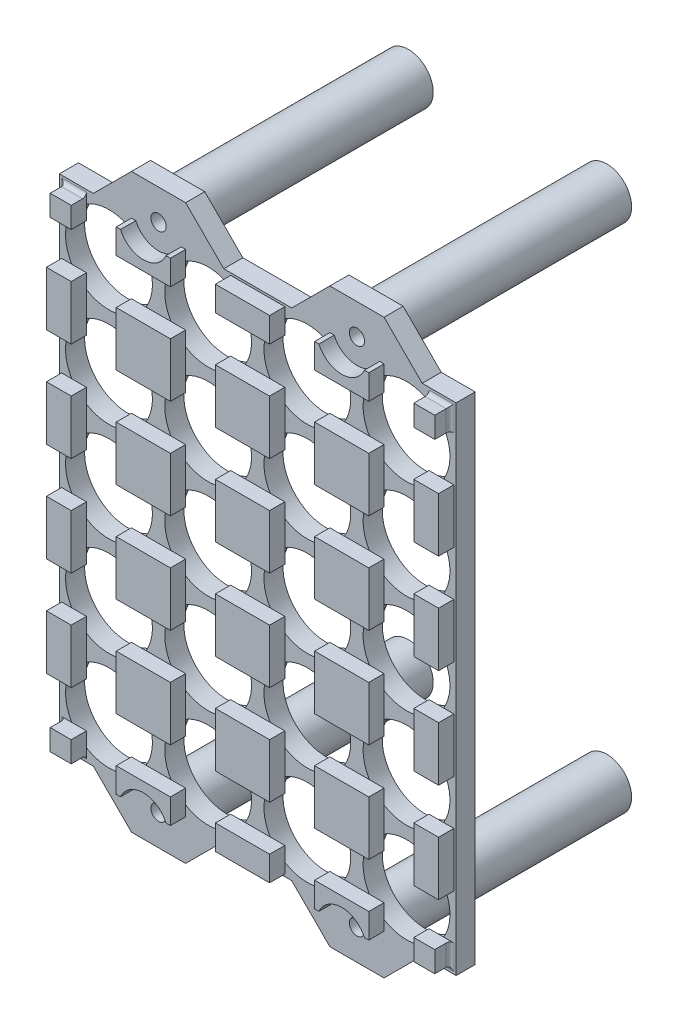
SolidWorks part; units mm, degrees
ref_plane "Front Plane" through (0, 0, 0) normal (0, 0, 1) x (1, 0, 0)
ref_plane "Top Plane" through (0, 0, 0) normal (0, 1, 0) x (1, 0, 0)
ref_plane "Right Plane" through (0, 0, 0) normal (1, 0, 0) x (0, 0, -1)
sketch "Szkic1" plane through (0, 0, 0) normal (0, 0, 1) x (1, 0, 0)
  line L1 (-20.2054, 8.0552) -> (83.7946, 8.0552)
  line L2 (-20.2054, 8.0552) -> (-20.2054, -17.9448)
  line L3 (-20.2054, -17.9448) -> (83.7946, -17.9448)
  line L4 (83.7946, 8.0552) -> (83.7946, -17.9448)
  circle A0 centre (-7.2054, -4.9448) radius 8.854
  circle A1 centre (-7.2054, -4.9448) radius 11.3761
  circle A2 centre (18.7946, -4.9448) radius 8.854
  circle A3 centre (18.7946, -4.9448) radius 11.3761
  circle A4 centre (44.7946, -4.9448) radius 8.854
  circle A5 centre (44.7946, -4.9448) radius 11.3761
  circle A6 centre (70.7946, -4.9448) radius 8.854
  circle A7 centre (70.7946, -4.9448) radius 11.3761
  circle A10 centre (96.7946, -4.9448) radius 8.854 [skipped]
  circle A11 centre (96.7946, -4.9448) radius 11.3761 [skipped]
  dimension "D2" = 13
  dimension "D5" = 13
  dimension "D1" = 5
extrude "Dodanie-wyciągnięcie1" add sketch "Szkic1" along normal blind 5 contours L4 L1 L2 L3 A7 A5 A3 A1 region at (31.7946, -4.9448, 0)
sketch "Szkic15" plane through (0, 0, 0) normal (0, 0, 1) x (1, 0, 0)
  line L6 (-20.2054, -4.9448) -> (-32.3088, -4.9448)
  line L41 (-18.6054, 6.4552) -> (-13.1054, 6.4552)
  line L42 (-18.6054, 6.4552) -> (-18.6054, 0.9552)
  line L43 (-18.6054, 0.9552) -> (-13.1054, 0.9552)
  line L44 (-13.1054, 6.4552) -> (-13.1054, 0.9552)
  line L45 (4.1946, 0.9552) -> (-1.3054, 0.9552)
  line L46 (4.1946, 6.4552) -> (4.1946, 0.9552)
  line L47 (4.1946, 6.4552) -> (-1.3054, 6.4552)
  line L48 (-1.3054, 6.4552) -> (-1.3054, 0.9552)
  line L49 (7.3946, 0.9552) -> (12.8946, 0.9552)
  line L50 (12.8946, 6.4552) -> (12.8946, 0.9552)
  line L51 (7.3946, 6.4552) -> (12.8946, 6.4552)
  line L52 (7.3946, 6.4552) -> (7.3946, 0.9552)
  line L53 (30.1946, 6.4552) -> (24.6946, 6.4552)
  line L54 (24.6946, 6.4552) -> (24.6946, 0.9552)
  line L55 (30.1946, 6.4552) -> (30.1946, 0.9552)
  line L56 (30.1946, 0.9552) -> (24.6946, 0.9552)
  line L57 (33.3946, 0.9552) -> (38.8946, 0.9552)
  line L58 (38.8946, 6.4552) -> (38.8946, 0.9552)
  line L59 (33.3946, 6.4552) -> (38.8946, 6.4552)
  line L60 (33.3946, 6.4552) -> (33.3946, 0.9552)
  line L61 (56.1946, 6.4552) -> (50.6946, 6.4552)
  line L62 (50.6946, 6.4552) -> (50.6946, 0.9552)
  line L63 (56.1946, 6.4552) -> (56.1946, 0.9552)
  line L64 (56.1946, 0.9552) -> (50.6946, 0.9552)
  line L65 (59.3946, 0.9552) -> (64.8946, 0.9552)
  line L66 (64.8946, 6.4552) -> (64.8946, 0.9552)
  line L67 (59.3946, 6.4552) -> (64.8946, 6.4552)
  line L68 (59.3946, 6.4552) -> (59.3946, 0.9552)
  line L69 (82.1946, 6.4552) -> (76.6946, 6.4552)
  line L70 (76.6946, 6.4552) -> (76.6946, 0.9552)
  line L71 (82.1946, 6.4552) -> (82.1946, 0.9552)
  line L72 (82.1946, 0.9552) -> (76.6946, 0.9552)
  line L105 (56.1946, -7.5448) -> (50.6946, -7.5448) [skipped]
  line L106 (56.1946, -7.5448) -> (56.1946, -13.0448) [skipped]
  line L107 (56.1946, -13.0448) -> (50.6946, -13.0448) [skipped]
  line L108 (59.3946, -13.0448) -> (64.8946, -13.0448) [skipped]
  line L109 (64.8946, -7.5448) -> (64.8946, -13.0448) [skipped]
  line L110 (59.3946, -7.5448) -> (64.8946, -7.5448) [skipped]
  line L111 (59.3946, -7.5448) -> (59.3946, -13.0448) [skipped]
  line L112 (82.1946, -7.5448) -> (76.6946, -7.5448) [skipped]
  line L113 (76.6946, -7.5448) -> (76.6946, -13.0448) [skipped]
  line L114 (82.1946, -7.5448) -> (82.1946, -13.0448) [skipped]
  line L115 (82.1946, -13.0448) -> (76.6946, -13.0448) [skipped]
  line L116 (7.3946, -13.0448) -> (12.8946, -13.0448) [skipped]
  line L117 (12.8946, -7.5448) -> (12.8946, -13.0448) [skipped]
  line L118 (7.3946, -7.5448) -> (12.8946, -7.5448) [skipped]
  line L119 (7.3946, -7.5448) -> (7.3946, -13.0448) [skipped]
  line L120 (30.1946, -7.5448) -> (24.6946, -7.5448) [skipped]
  line L121 (24.6946, -7.5448) -> (24.6946, -13.0448) [skipped]
  line L122 (30.1946, -7.5448) -> (30.1946, -13.0448) [skipped]
  line L123 (30.1946, -13.0448) -> (24.6946, -13.0448) [skipped]
  line L124 (33.3946, -13.0448) -> (38.8946, -13.0448) [skipped]
  line L125 (38.8946, -7.5448) -> (38.8946, -13.0448) [skipped]
  line L126 (33.3946, -7.5448) -> (38.8946, -7.5448) [skipped]
  line L127 (33.3946, -7.5448) -> (33.3946, -13.0448) [skipped]
  line L128 (50.6946, -7.5448) -> (50.6946, -13.0448) [skipped]
  line L129 (-18.6054, -13.0448) -> (-13.1054, -13.0448) [skipped]
  line L130 (-13.1054, -7.5448) -> (-13.1054, -13.0448) [skipped]
  line L131 (-18.6054, -7.5448) -> (-13.1054, -7.5448) [skipped]
  line L132 (-18.6054, -7.5448) -> (-18.6054, -13.0448) [skipped]
  line L133 (4.1946, -7.5448) -> (-1.3054, -7.5448) [skipped]
  line L134 (-1.3054, -7.5448) -> (-1.3054, -13.0448) [skipped]
  line L135 (4.1946, -7.5448) -> (4.1946, -13.0448) [skipped]
  line L136 (4.1946, -13.0448) -> (-1.3054, -13.0448) [skipped]
  line L138 (82.1946, -10.8448) -> (76.6946, -10.8448)
  line L139 (82.1946, -16.3448) -> (82.1946, -10.8448)
  line L140 (76.6946, -16.3448) -> (76.6946, -10.8448)
  line L141 (82.1946, -16.3448) -> (76.6946, -16.3448)
  line L142 (59.3946, -16.3448) -> (59.3946, -10.8448)
  line L143 (59.3946, -16.3448) -> (64.8946, -16.3448)
  line L144 (64.8946, -16.3448) -> (64.8946, -10.8448)
  line L145 (59.3946, -10.8448) -> (64.8946, -10.8448)
  line L146 (56.1946, -10.8448) -> (50.6946, -10.8448)
  line L147 (56.1946, -16.3448) -> (56.1946, -10.8448)
  line L148 (50.6946, -16.3448) -> (50.6946, -10.8448)
  line L149 (56.1946, -16.3448) -> (50.6946, -16.3448)
  line L150 (33.3946, -16.3448) -> (33.3946, -10.8448)
  line L151 (33.3946, -16.3448) -> (38.8946, -16.3448)
  line L152 (38.8946, -16.3448) -> (38.8946, -10.8448)
  line L153 (33.3946, -10.8448) -> (38.8946, -10.8448)
  line L154 (30.1946, -10.8448) -> (24.6946, -10.8448)
  line L155 (30.1946, -16.3448) -> (30.1946, -10.8448)
  line L156 (24.6946, -16.3448) -> (24.6946, -10.8448)
  line L157 (30.1946, -16.3448) -> (24.6946, -16.3448)
  line L158 (7.3946, -16.3448) -> (7.3946, -10.8448)
  line L159 (7.3946, -16.3448) -> (12.8946, -16.3448)
  line L160 (12.8946, -16.3448) -> (12.8946, -10.8448)
  line L161 (7.3946, -10.8448) -> (12.8946, -10.8448)
  line L162 (-1.3054, -16.3448) -> (-1.3054, -10.8448)
  line L163 (4.1946, -16.3448) -> (-1.3054, -16.3448)
  line L164 (4.1946, -16.3448) -> (4.1946, -10.8448)
  line L165 (4.1946, -10.8448) -> (-1.3054, -10.8448)
  line L166 (-13.1054, -16.3448) -> (-13.1054, -10.8448)
  line L167 (-18.6054, -10.8448) -> (-13.1054, -10.8448)
  line L168 (-18.6054, -16.3448) -> (-18.6054, -10.8448)
  line L169 (-18.6054, -16.3448) -> (-13.1054, -16.3448)
  point P5 (-18.6054, 6.4552)
  point P71 (-18.6054, -16.3448)
  dimension "D1" = 5.5
extrude "Dodanie-wyciągnięcie7" add sketch "Szkic15" along normal blind 4 from surface contours L167 L166 L169 L168 | L41 L44 L43 L42 | L47 L48 L45 L46 | L51 L50 L49 L52 | L165 L162 L163 L164 | L161 L160 L159 L158 | L53 L54 L56 L55 | L59 L58 L57 L60 | L153 L152 L151 L150 | L154 L156 L157 L155 | L61 L62 L64 L63 | L67 L66 L65 L68 | L145 L144 L143 L142 | L146 L148 L149 L147 | L69 L70 L72 L71 | L138 L140 L141 L139 starting at face at (82.1707, -4.9448, 5)
fillet "Zaokrąglenie9" radius 1 32 edges at (82.1946, 3.7052, 5) (79.4446, 6.4552, 5) (82.1946, -13.5948, 5) (79.4446, -16.3448, 5) (59.3946, 3.7052, 5) (62.1446, 6.4552, 5) (59.3946, -13.5948, 5) (62.1446, -16.3448, 5) (53.4446, -16.3448, 5) (56.1946, -13.5948, 5) (56.1946, 3.7052, 5) (53.4446, 6.4552, 5) (36.1446, 6.4552, 5) (33.3946, 3.7052, 5) (33.3946, -13.5948, 5) (36.1446, -16.3448, 5) (27.4446, -16.3448, 5) (30.1946, -13.5948, 5) (30.1946, 3.7052, 5) (27.4446, 6.4552, 5) (-18.6054, -13.5948, 5) (-15.8554, -16.3448, 5) (10.1446, -16.3448, 5) (1.4446, -16.3448, 5) (4.1946, -13.5948, 5) (7.3946, -13.5948, 5) (7.3946, 3.7052, 5) (10.1446, 6.4552, 5) (4.1946, 3.7052, 5) (1.4446, 6.4552, 5) (-15.8554, 6.4552, 5) (-18.6054, 3.7052, 5)
pattern_linear "Szyk liniowy9" count 5 spacing 26 along (0, 1, 0) of "Dodanie-wyciągnięcie1", "Dodanie-wyciągnięcie7", "Zaokrąglenie9"
sketch "Szkic16" plane through (0, 0, 5) normal (0, 0, 1) x (1, 0, 0)
  line L1 (-1.3054, 93.1552) -> (12.8946, 93.1552)
  line L2 (-1.3054, 93.1552) -> (-1.3054, 78.9552)
  line L3 (-1.3054, 78.9552) -> (12.8946, 78.9552)
  line L4 (12.8946, 93.1552) -> (12.8946, 78.9552)
  line L5 (24.6946, 93.1552) -> (38.8946, 93.1552)
  line L6 (24.6946, 93.1552) -> (24.6946, 78.9552)
  line L7 (24.6946, 78.9552) -> (38.8946, 78.9552)
  line L8 (38.8946, 93.1552) -> (38.8946, 78.9552)
  line L9 (50.6946, 93.1552) -> (64.8946, 93.1552)
  line L10 (50.6946, 93.1552) -> (50.6946, 78.9552)
  line L11 (50.6946, 78.9552) -> (64.8946, 78.9552)
  line L12 (64.8946, 93.1552) -> (64.8946, 78.9552)
  line L13 (-1.3054, 67.1552) -> (12.8946, 67.1552)
  line L14 (-1.3054, 67.1552) -> (-1.3054, 52.9552)
  line L15 (-1.3054, 52.9552) -> (12.8946, 52.9552)
  line L16 (12.8946, 67.1552) -> (12.8946, 52.9552)
  line L17 (24.6946, 67.1552) -> (38.8946, 67.1552)
  line L18 (24.6946, 67.1552) -> (24.6946, 52.9552)
  line L19 (24.6946, 52.9552) -> (38.8946, 52.9552)
  line L20 (38.8946, 67.1552) -> (38.8946, 52.9552)
  line L21 (50.6946, 67.1552) -> (64.8946, 67.1552)
  line L22 (50.6946, 67.1552) -> (50.6946, 52.9552)
  line L23 (50.6946, 52.9552) -> (64.8946, 52.9552)
  line L24 (64.8946, 67.1552) -> (64.8946, 52.9552)
  line L25 (50.6946, 41.1552) -> (64.8946, 41.1552)
  line L26 (50.6946, 41.1552) -> (50.6946, 26.9552)
  line L27 (50.6946, 26.9552) -> (64.8946, 26.9552)
  line L28 (64.8946, 41.1552) -> (64.8946, 26.9552)
  line L29 (24.6946, 41.1552) -> (38.8946, 41.1552)
  line L30 (24.6946, 41.1552) -> (24.6946, 26.9552)
  line L31 (24.6946, 26.9552) -> (38.8946, 26.9552)
  line L32 (38.8946, 41.1552) -> (38.8946, 26.9552)
  line L33 (-1.3054, 41.1552) -> (12.8946, 41.1552)
  line L34 (-1.3054, 41.1552) -> (-1.3054, 26.9552)
  line L35 (-1.3054, 26.9552) -> (12.8946, 26.9552)
  line L36 (12.8946, 41.1552) -> (12.8946, 26.9552)
  line L37 (-1.3054, 15.1552) -> (12.8946, 15.1552)
  line L38 (-1.3054, 15.1552) -> (-1.3054, 0.9552)
  line L39 (-1.3054, 0.9552) -> (12.8946, 0.9552)
  line L40 (12.8946, 15.1552) -> (12.8946, 0.9552)
  line L41 (24.6946, 15.1552) -> (38.8946, 15.1552)
  line L42 (24.6946, 15.1552) -> (24.6946, 0.9552)
  line L43 (24.6946, 0.9552) -> (38.8946, 0.9552)
  line L44 (38.8946, 15.1552) -> (38.8946, 0.9552)
  line L45 (50.6946, 15.1552) -> (64.8946, 15.1552)
  line L46 (50.6946, 15.1552) -> (50.6946, 0.9552)
  line L47 (50.6946, 0.9552) -> (64.8946, 0.9552)
  line L48 (64.8946, 15.1552) -> (64.8946, 0.9552)
  line L49 (-1.3054, 111.4552) -> (12.8946, 111.4552)
  line L50 (-1.3054, 111.4552) -> (-1.3054, 104.9552)
  line L51 (-1.3054, 104.9552) -> (12.8946, 104.9552)
  line L52 (12.8946, 111.4552) -> (12.8946, 104.9552)
  line L53 (24.6946, 111.4552) -> (38.8946, 111.4552)
  line L54 (24.6946, 111.4552) -> (24.6946, 104.9552)
  line L55 (24.6946, 104.9552) -> (38.8946, 104.9552)
  line L56 (38.8946, 111.4552) -> (38.8946, 104.9552)
  line L57 (50.6946, 111.4552) -> (64.8946, 111.4552)
  line L58 (50.6946, 111.4552) -> (50.6946, 104.9552)
  line L59 (50.6946, 104.9552) -> (64.8946, 104.9552)
  line L60 (64.8946, 111.4552) -> (64.8946, 104.9552)
  line L61 (76.6946, 93.1552) -> (83.1946, 93.1552)
  line L62 (76.6946, 93.1552) -> (76.6946, 78.9552)
  line L63 (76.6946, 78.9552) -> (83.1946, 78.9552)
  line L64 (83.1946, 93.1552) -> (83.1946, 78.9552)
  line L65 (76.6946, 67.1552) -> (83.1946, 67.1552)
  line L66 (76.6946, 67.1552) -> (76.6946, 52.9552)
  line L67 (76.6946, 52.9552) -> (83.1946, 52.9552)
  line L68 (83.1946, 67.1552) -> (83.1946, 52.9552)
  line L69 (76.6946, 41.1552) -> (83.1946, 41.1552)
  line L70 (76.6946, 41.1552) -> (76.6946, 26.9552)
  line L71 (76.6946, 26.9552) -> (83.1946, 26.9552)
  line L72 (83.1946, 41.1552) -> (83.1946, 26.9552)
  line L73 (76.6946, 15.1552) -> (83.1946, 15.1552)
  line L74 (76.6946, 15.1552) -> (76.6946, 0.9552)
  line L75 (76.6946, 0.9552) -> (83.1946, 0.9552)
  line L76 (83.1946, 15.1552) -> (83.1946, 0.9552)
  line L77 (50.6946, -10.8448) -> (64.8946, -10.8448)
  line L78 (50.6946, -10.8448) -> (50.6946, -17.3448)
  line L79 (50.6946, -17.3448) -> (64.8946, -17.3448)
  line L80 (64.8946, -10.8448) -> (64.8946, -17.3448)
  line L81 (24.6946, -10.8448) -> (38.8946, -10.8448)
  line L82 (24.6946, -10.8448) -> (24.6946, -17.3448)
  line L83 (24.6946, -17.3448) -> (38.8946, -17.3448)
  line L84 (38.8946, -10.8448) -> (38.8946, -17.3448)
  line L85 (-1.3054, -10.8448) -> (12.8946, -10.8448)
  line L86 (-1.3054, -10.8448) -> (-1.3054, -17.3448)
  line L87 (-1.3054, -17.3448) -> (12.8946, -17.3448)
  line L88 (12.8946, -10.8448) -> (12.8946, -17.3448)
  line L89 (-19.6054, 15.1552) -> (-13.1054, 15.1552)
  line L90 (-19.6054, 15.1552) -> (-19.6054, 0.9552)
  line L91 (-19.6054, 0.9552) -> (-13.1054, 0.9552)
  line L92 (-13.1054, 15.1552) -> (-13.1054, 0.9552)
  line L93 (-19.6054, 41.1552) -> (-13.1054, 41.1552)
  line L94 (-19.6054, 41.1552) -> (-19.6054, 26.9552)
  line L95 (-19.6054, 26.9552) -> (-13.1054, 26.9552)
  line L96 (-13.1054, 41.1552) -> (-13.1054, 26.9552)
  line L97 (-19.6054, 67.1552) -> (-13.1054, 67.1552)
  line L98 (-19.6054, 67.1552) -> (-19.6054, 52.9552)
  line L99 (-19.6054, 52.9552) -> (-13.1054, 52.9552)
  line L100 (-13.1054, 67.1552) -> (-13.1054, 52.9552)
  line L101 (-19.6054, 93.1552) -> (-13.1054, 93.1552)
  line L102 (-19.6054, 93.1552) -> (-19.6054, 78.9552)
  line L103 (-19.6054, 78.9552) -> (-13.1054, 78.9552)
  line L104 (-13.1054, 93.1552) -> (-13.1054, 78.9552)
extrude "Dodanie-wyciągnięcie8" add sketch "Szkic16" along normal blind 4
sketch "Szkic17" plane through (0, 112.0552, 0) normal (0, 1, 0) x (1, 0, 0)
  line L0 (-20.2054, 0) -> (83.7946, 0) construction
  line L1 (-1.3054, -5) -> (12.8946, -5)
  line L2 (-1.3054, -5) -> (-1.3054, 0)
  line L3 (-1.3054, 0) -> (12.8946, 0)
  line L4 (12.8946, -5) -> (12.8946, 0)
  line L5 (50.6946, -9) -> (50.6946, -5) construction
  line L6 (50.6946, 0) -> (64.8946, 0)
  line L7 (50.6946, 0) -> (50.6946, -5)
  line L8 (50.6946, -5) -> (64.8946, -5)
  line L9 (64.8946, 0) -> (64.8946, -5)
  dimension "D1" = 0
extrude "Dodanie-wyciągnięcie9" add sketch "Szkic17" along normal blind 10
ref_plane "Płaszczyzna4" through (0, 47.0552, 0) normal (0, 1, 0) x (1, 0, 0)
sketch "Szkic19" plane through (0, 0, 0) normal (0, 0, -1) x (-1, 0, 0)
  line L0 (-57.7946, 122.0552) -> (-57.7946, 106.6429)
  line L1 (-64.8946, 122.0552) -> (-50.6946, 122.0552) construction
  line L2 (-31.7946, 112.0552) -> (-31.7946, 127.0552)
  line L3 (-12.8946, 112.0552) -> (-50.6946, 112.0552) construction
  circle A0 centre (-57.7946, 114.0552) radius 2
  circle A1 centre (-57.7946, 114.0552) radius 6.5
  circle A2 centre (-70.7946, 99.0552) radius 11.3761 construction
  circle A3 centre (-5.7946, 114.0552) radius 2
  circle A4 centre (-5.7946, 114.0552) radius 6.5
  dimension "D1" = 4
  dimension "D2" = 4.5
  dimension "D3" = 15
extrude "Dodanie-wyciągnięcie10" add sketch "Szkic19" along normal blind 60.5 contours L0 A1 A0 | L0 A1 A0 | A4 A3 region at (54.8362, 114.0552, 0) region at (60.753, 114.0552, 0) region at (12.1107, 114.0552, 0)
extrude "Wytnij-wyciągnięcie2" cut sketch "Szkic19<4>" against normal blind 10 contours A0 | A3
sketch "Szkic19<4>" plane through (0, 0, 0) normal (0, 0, -1) x (-1, 0, 0) same geometry as "Szkic19"
extrude "Wytnij-wyciągnięcie4" cut sketch "Szkic19<6>" against normal blind 10 from surface contours A1 | A4 starting at face at (57.7946, 21.0552, 5)
sketch "Szkic19<6>" plane through (0, 0, 0) normal (0, 0, -1) x (-1, 0, 0) same geometry as "Szkic19"
mirror "Lustro11" about plane through (0, 47.0552, 0) normal (0, 1, 0) of "Wytnij-wyciągnięcie4", "Dodanie-wyciągnięcie9", "Dodanie-wyciągnięcie10", "Wytnij-wyciągnięcie2"
chamfer "Sfazowanie2" distance 10 angle 45 7 edges at (64.8946, -17.9448, 2.5) (50.6946, -17.9448, 2.5) (-1.3054, -17.9448, 2.5) (-1.3054, 112.0552, 2.5) (12.8946, 112.0552, 2.5) (50.6946, 112.0552, 2.5) (64.8946, 112.0552, 2.5)
chamfer "Sfazowanie3" distance 10 angle 45 1 edges at (12.8946, -17.9448, 2.5)
